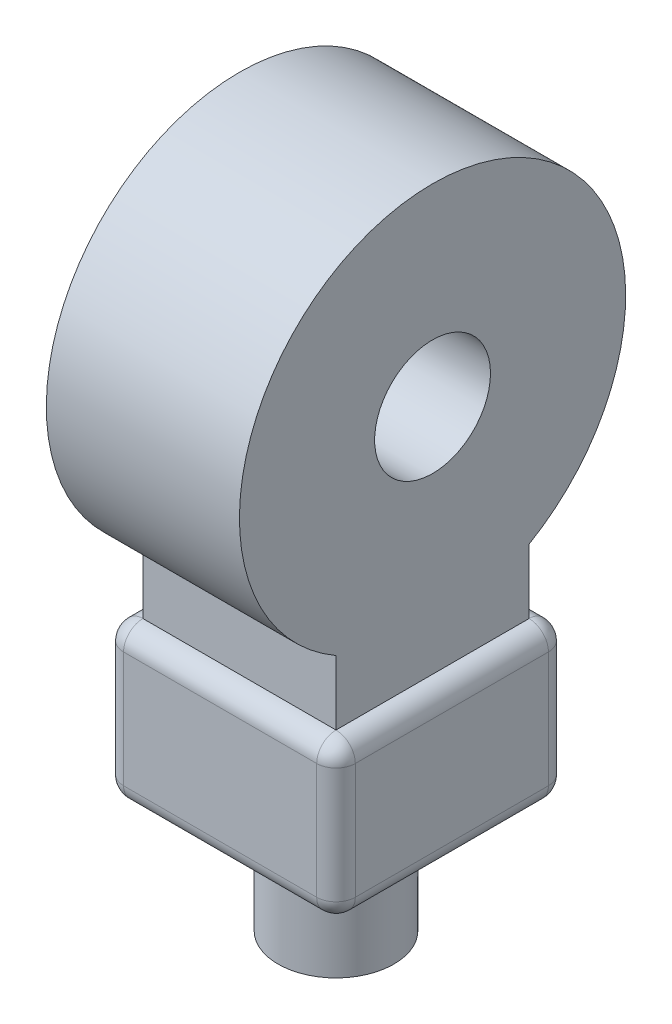
SolidWorks part; units mm, degrees
ref_plane "前基準面" through (0, 0, 0) normal (0, 0, 1) x (1, 0, 0)
ref_plane "上基準面" through (0, 0, 0) normal (0, 1, 0) x (1, 0, 0)
ref_plane "右基準面" through (0, 0, 0) normal (1, 0, 0) x (0, 0, -1)
sketch "草圖1" plane through (0, 0, 0) normal (0, 1, 0) x (1, 0, 0)
  line L1 (-30, -30) -> (30, -30)
  line L2 (-30, -30) -> (-30, 30)
  line L3 (-30, 30) -> (30, 30)
  line L4 (30, -30) -> (30, 30)
  line L5 (-30, -30) -> (30, 30) construction
  line L6 (-30, 30) -> (30, -30) construction
  circle A0 centre (0, 0) radius 50 construction
  dimension "D1" = 100
  dimension "D2" = 60
  dimension "D3" = 60
extrude "填料-伸長1" add sketch "草圖1" along normal blind 40
sketch "草圖2" plane through (0, 0, 0) normal (0, -1, 0) x (1, 0, 0)
  circle A0 centre (0, 0) radius 15
  dimension "D1" = 30
extrude "填料-伸長2" add sketch "草圖2" along normal blind 30
sketch "草圖3" plane through (0, 0, 0) normal (1, 0, 0) x (0, 0, -1)
  line L0 (-30, 40) -> (30, 40) construction
  line L1 (-25, 40) -> (25, 40)
  line L2 (-25, 40) -> (-25, 56.6987)
  line L4 (25, 40) -> (25, 56.6987)
  line L5 (0, 0) -> (0, 90) construction
  arc A0 (25, 56.6987) -> (-25, 56.6987) centre (0, 100) ccw
  circle A1 centre (0, 100) radius 15
  dimension "D3" = 100
  dimension "D1" = 30
  dimension "D2" = 60
  dimension "D4" = 50
extrude "填料-伸長3" add sketch "草圖3" along normal mid plane 50
fillet "圓角11" radius 5 12 edges at (-30, 40, 0) (-30, 0, 0) (0, 40, -30) (-30, 20, -30) (0, 0, -30) (30, 40, 0) (30, 20, -30) (30, 0, 0) (-30, 20, 30) (0, 40, 30) (30, 20, 30) (0, 0, 30)
